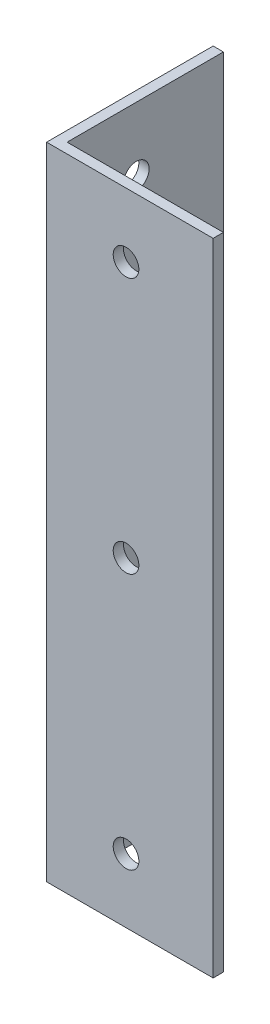
SolidWorks part; units mm, degrees
ref_plane "Спереди" through (0, 0, 0) normal (0, 0, 1) x (1, 0, 0)
ref_plane "Сверху" through (0, 0, 0) normal (0, 1, 0) x (1, 0, 0)
ref_plane "Справа" through (0, 0, 0) normal (1, 0, 0) x (0, 0, -1)
sketch "Эскиз1" plane through (0, 0, 0) normal (0, 1, 0) x (1, 0, 0)
  line L0 (0, 0) -> (65, 0)
  line L1 (0, 0) -> (0, 65)
extrude "Вытянуть-Тонкостенный1" add sketch "Эскиз1" along normal blind 250 thin thin type one direction wall 4
sketch "Эскиз6" plane through (0, 0, 0) normal (-1, 0, 0) x (0, 0, 1)
  circle A0 centre (-31, 25) radius 5
  circle A1 centre (-31, 125) radius 5
  circle A2 centre (-31, 225) radius 5
  dimension "D1" = 3
extrude "Вырез-Вытянуть1" cut sketch "Эскиз6" against normal blind 10
sketch "Эскиз7" plane through (0, 0, 0) normal (0, 0, 1) x (1, 0, 0)
  circle A0 centre (31, 25) radius 5
  circle A1 centre (31, 125) radius 5
  circle A2 centre (31, 225) radius 5
  dimension "D1" = 3
extrude "Вырез-Вытянуть2" cut sketch "Эскиз7" against normal blind 10
